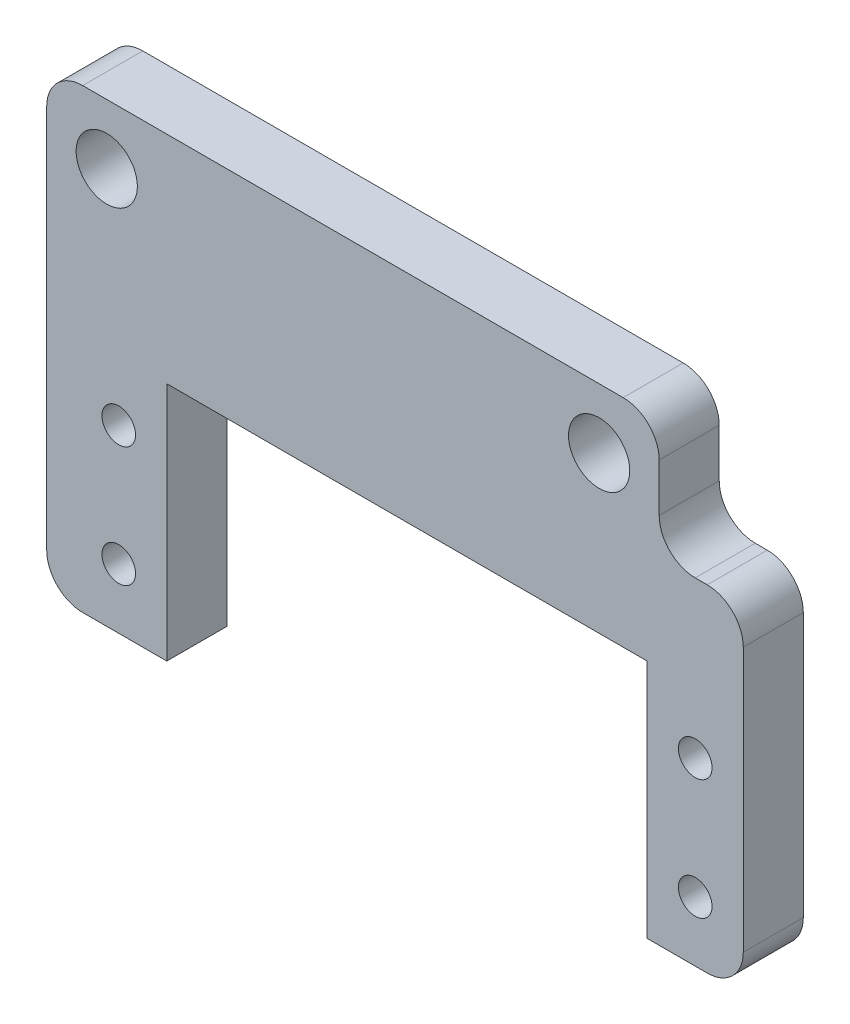
SolidWorks part; units mm, degrees
ref_plane "Front Plane" through (0, 0, 0) normal (0, 0, 1) x (1, 0, 0)
ref_plane "Top Plane" through (0, 0, 0) normal (0, 1, 0) x (1, 0, 0)
ref_plane "Right Plane" through (0, 0, 0) normal (1, 0, 0) x (0, 0, -1)
sketch "Sketch1" plane through (0, 0, 0) normal (0, 0, 1) x (1, 0, 0)
  line L0 (0, 5) -> (51, 5) construction
  line L1 (0, 0) -> (51, 0)
  line L2 (0, 0) -> (0, 10)
  line L3 (0, 10) -> (51, 10)
  line L4 (51, 0) -> (51, 10)
  circle A0 centre (5, 5) radius 2.55
  circle A1 centre (46, 5) radius 2.55
  dimension "D5" = 5.1
  dimension "D1" = 10
  dimension "D2" = 41
  dimension "D3" = 5
  dimension "D4" = 5
extrude "Boss-Extrude1" add sketch "Sketch1" along normal blind 5
sketch "Sketch2" plane through (0, 0, 5) normal (0, 0, 1) x (1, 0, 0)
  line L0 (0, 10) -> (0, 0) construction
  line L1 (10, -28) -> (50, -28) construction
  line L2 (10, -28) -> (10, -8)
  line L3 (10, -8) -> (50, -8)
  line L4 (50, -28) -> (50, -8)
  line L5 (0, 0) -> (51, 0) construction
  line L6 (10, -28) -> (0, -28)
  line L7 (0, -28) -> (0, 0)
  line L8 (0, 0) -> (51, 0)
  line L9 (51, 0) -> (58, 0)
  line L10 (58, 0) -> (58, -28)
  line L11 (58, -28) -> (50, -28)
  line L12 (6, -28) -> (6, 0) construction
  line L13 (30, -8) -> (30, -28) construction
  circle A0 centre (6, -23) radius 1.4
  circle A1 centre (6, -13) radius 1.4
  circle A2 centre (54, -23) radius 1.4
  circle A3 centre (54, -13) radius 1.4
  dimension "D9" = 2.8
  dimension "D1" = 40
  dimension "D2" = 20
  dimension "D3" = 10
  dimension "D4" = 8
  dimension "D5" = 8
  dimension "D6" = 4
  dimension "D7" = 10
  dimension "D8" = 5
extrude "Boss-Extrude2" add sketch "Sketch2" against normal blind 5
fillet "Fillet1" radius 3 6 edges at (0, -28, 2.5) (58, -28, 2.5) (58, 0, 2.5) (0, 10, 2.5) (51, 10, 2.5) (51, 0, 2.5)
sketch "Sketch3" plane through (0, 0, 5) normal (0, 0, 1) x (1, 0, 0)
  line L1 (3, -28) -> (10, -28) construction
  line L2 (10, -8) -> (50, -8) construction
  line L3 (50, -8) -> (50, -28) construction
  circle A0 centre (40, -18) radius 10
